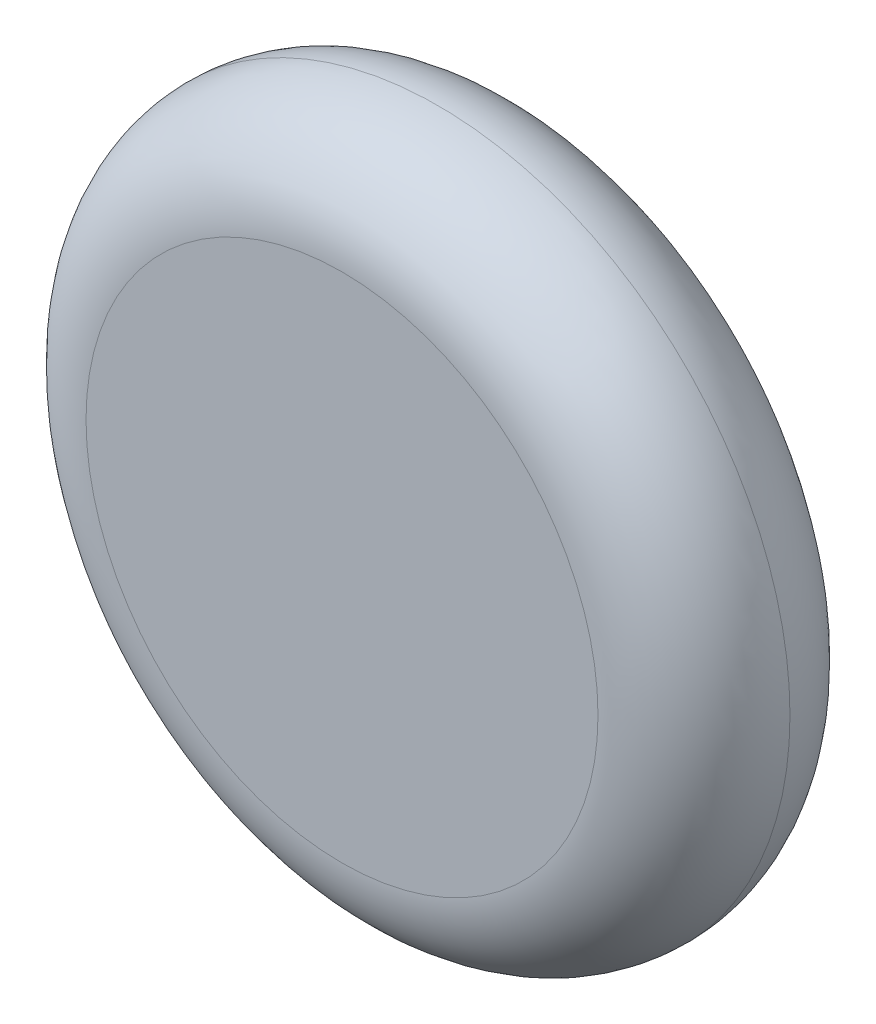
SolidWorks part; units mm, degrees
ref_plane "Front Plane" through (0, 0, 0) normal (0, 0, 1) x (1, 0, 0)
ref_plane "Top Plane" through (0, 0, 0) normal (0, 1, 0) x (1, 0, 0)
ref_plane "Right Plane" through (0, 0, 0) normal (1, 0, 0) x (0, 0, -1)
sketch "Sketch1" plane through (0, 0, 0) normal (0, 0, 1) x (1, 0, 0)
  circle A0 centre (0, 0) radius 26.95
extrude "Boss-Extrude1" add sketch "Sketch1" along normal blind 14.7
fillet "Fillet1" radius 7.35 1 edges at (26.95, 0, 14.7)
fillet "Fillet2" radius 7.35 1 edges at (26.95, 0, 0)
